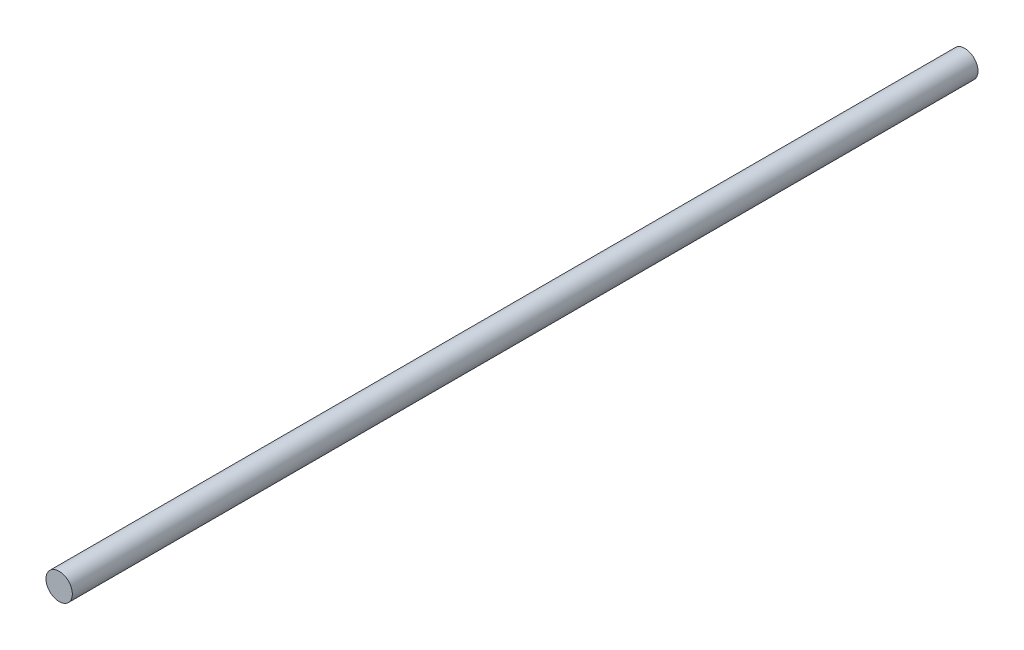
SolidWorks part; units mm, degrees
ref_plane "Front Plane" through (0, 0, 0) normal (0, 0, 1) x (1, 0, 0)
ref_plane "Top Plane" through (0, 0, 0) normal (0, 1, 0) x (1, 0, 0)
ref_plane "Right Plane" through (0, 0, 0) normal (1, 0, 0) x (0, 0, -1)
sketch "Sketch1" plane through (0, 0, 0) normal (0, 0, 1) x (1, 0, 0)
  circle A0 centre (0, 0) radius 4
  dimension "D1" = 8
extrude "Boss-Extrude1" add sketch "Sketch1" along normal blind 137.5 and the other way blind 137.5
